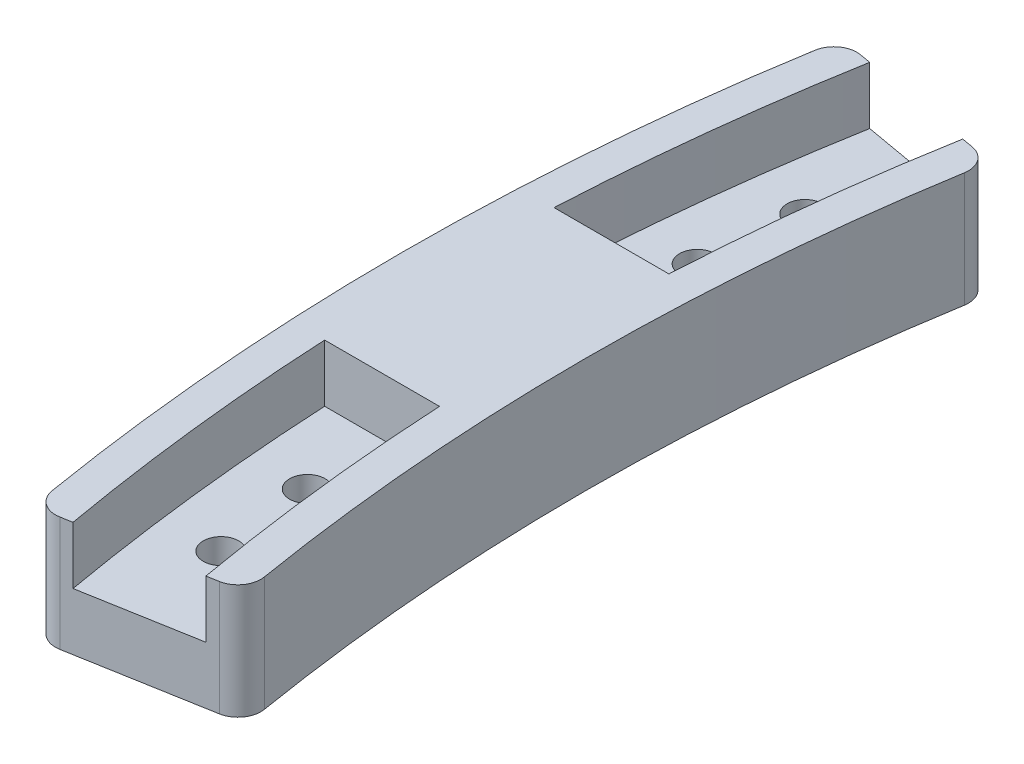
SolidWorks part; units mm, degrees
ref_plane "Front Plane" through (0, 0, 0) normal (0, 0, 1) x (1, 0, 0)
ref_plane "Top Plane" through (0, 0, 0) normal (0, 1, 0) x (1, 0, 0)
ref_plane "Right Plane" through (0, 0, 0) normal (1, 0, 0) x (0, 0, -1)
sketch "Sketch1" plane through (0, 0, 0) normal (0, 1, 0) x (1, 0, 0)
  line L0 (0, 0) -> (-196.9616, -34.7296) construction
  line L1 (0, 0) -> (-196.9616, 34.7296) construction
  line L2 (0, 0) -> (-195, 0) construction
  line L3 (-196.9616, 34.7296) -> (-187.1135, 32.9932)
  line L4 (-187.1135, -32.9932) -> (-196.9616, -34.7296)
  line L5 (0, 0) -> (-199.916, -35.2506) construction
  line L6 (0, 0) -> (-199.916, 35.2506) construction
  line L7 (-199.916, 35.2506) -> (-184.159, 32.4722)
  line L8 (-199.916, -35.2506) -> (-184.159, -32.4722)
  arc A0 (-196.9616, 34.7296) -> (-196.9616, -34.7296) centre (0, 0) ccw
  arc A1 (-187.1135, 32.9932) -> (-187.1135, -32.9932) centre (0, 0) ccw
  arc A2 (-192.0375, -33.8614) -> (-192.0375, 33.8614) centre (0, 0) cw construction
  arc A4 (-184.159, 32.4722) -> (-184.159, -32.4722) centre (0, 0) ccw
  arc A5 (-199.916, 35.2506) -> (-199.916, -35.2506) centre (0, 0) ccw
  dimension "D1" = 200
  dimension "D2" = 190
  dimension "D3" = 5
  dimension "D5" = 187
  dimension "D6" = 203
  dimension "D4" = 20
extrude "Boss-Extrude1" add sketch "Sketch1" along normal blind 10 contours A1 L3 A0 L4 | L7 A5 L8 A0 | A4 L7 A1 L8 region at (-200.4823, 0, 0) region at (-194.054, 0, 0) region at (-187.5484, 0, 0)
ref_plane "Plane1" through (-195, 0, 0) normal (1, 0, 0) x (0, 0, -1)
sketch "Sketch15" plane through (0, 10, 0) normal (0, 1, 0) x (1, 0, 0)
  line L0 (-187.1135, -32.9932) -> (-196.9616, -34.7296) construction
  line L1 (-185, 10) -> (-205, 10)
  line L2 (-185, 10) -> (-185, -10)
  line L3 (-185, -10) -> (-205, -10)
  line L4 (-205, 10) -> (-205, -10)
  line L5 (-185, 10) -> (-205, -10) construction
  line L6 (-185, -10) -> (-205, 10) construction
  line L7 (-196.9616, 34.7296) -> (-187.1135, 32.9932) construction
  line L8 (-187.1135, -32.9932) -> (-196.9616, -34.7296)
  line L9 (-196.9616, 34.7296) -> (-187.1135, 32.9932)
  arc A2 (-187.1135, 32.9932) -> (-187.1135, -32.9932) centre (0, 0) ccw construction
  arc A3 (-196.9616, 34.7296) -> (-196.9616, -34.7296) centre (0, 0) ccw construction
  arc A4 (-187.1135, 32.9932) -> (-187.1135, -32.9932) centre (0, 0) ccw
  arc A5 (-196.9616, 34.7296) -> (-196.9616, -34.7296) centre (0, 0) ccw
  point P0 (-195, 0)
  line M5 (-199.916, -35.2506) -> (-184.159, -32.4722)
  line M7 (-184.159, 32.4722) -> (-199.916, 35.2506)
  dimension "D1" = 20
  dimension "D2" = 20
extrude "Cut-Extrude1" cut sketch "Sketch15" against normal blind 5 contours A5 L1 A4 M7 | L3 A5 A4 M5 region at (-193.6958, 10, -21.9638) region at (-193.6958, 10, 21.9638)
ref_plane "Plane2" through (-195, 0, 0) normal (-1, 0, 0) x (0, 0, 1)
sketch "Sketch12" plane through (0, 0, 0) normal (0, 1, 0) x (1, 0, 0)
  line L0 (0, 0) -> (-194.258, -16.9954) construction
  line L1 (0, 0) -> (-193.3317, -25.4526) construction
  line L2 (0, 0) -> (-195, 0) construction
  line L3 (0, 0) -> (-195, 0) construction
  line L4 (0, 0) -> (-194.258, 16.9954) construction
  line L5 (0, 0) -> (-193.3317, 25.4526) construction
  arc A0 (-192.0375, 33.8614) -> (-192.0375, -33.8614) centre (0, 0) ccw construction
  dimension "D1" = 10
  dimension "D2" = 15
hole_wizard "Ø3.1 (3.1) Diameter Hole2" positions "Sketch18" profile "Sketch17" hole size "Ø3.1" standard "ISO" end condition through all
sketch "Sketch18" plane through (0, 0, 0) normal (0, -1, 0) x (-1, 0, 0)
  point P0 (193.3317, -25.4526)
  point P3 (194.258, -16.9954)
  point P6 (194.258, 16.9954)
  point P9 (193.3317, 25.4526)
sketch "Sketch17" plane through (-193.3317, 0, 25.4526) normal (1, 0, 0) x (0, 0, -1)
  line L0 (0, 0) -> (0, 10)
  line L1 (0, 10) -> (1.55, 10)
  line L2 (1.55, 10) -> (1.55, 0)
  line L5 (1.55, 0) -> (0, 0)
  line L11 (0, -6.35) -> (0, 107.95) construction
  dimension "Thru Hole Dia." = 3.1
  dimension "Thru Hole Depth" = 10
fillet "Fillet1" radius 2 4 edges at (-199.916, 5, -35.2506) (-184.159, 5, -32.4722) (-199.916, 5, 35.2506) (-184.159, 5, 32.4722)
